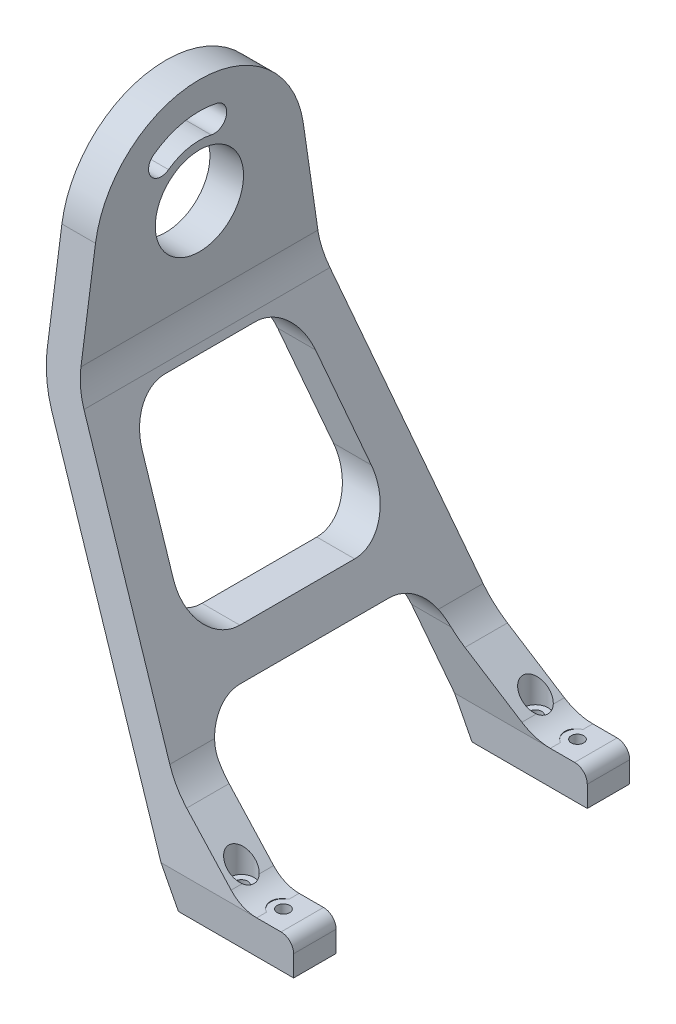
SolidWorks part; units mm, degrees
material "6061 合金"
ref_plane "前视基准面" through (0, 0, 0) normal (0, 0, 1) x (1, 0, 0)
ref_plane "上视基准面" through (0, 0, 0) normal (0, 1, 0) x (1, 0, 0)
ref_plane "右视基准面" through (0, 0, 0) normal (1, 0, 0) x (0, 0, -1)
sketch "草图1" plane through (0, 0, 0) normal (0, 0, 1) x (1, 0, 0)
  line L0 (0, 50) -> (0, 4.8715)
  line L1 (2.2402, -4.3258) -> (41.43, -80)
  line L2 (41.43, -80) -> (66.43, -80)
  arc A0 (2.2402, -4.3258) -> (0, 4.8715) centre (20, 4.8715) cw
  point P7 (0, 0)
  dimension "D5" = 20
  dimension "D1" = 80
  dimension "D2" = 41.43
  dimension "D3" = 50
  dimension "D4" = 25
extrude "拉伸-薄壁1" add sketch "草图1" along normal blind 80 thin thin type mid plane wall 8
sketch "草图9" plane through (0, 0, 0) normal (0, 0, -1) x (-1, 0, 0)
  line L0 (-53.9969, -76) -> (-36.0752, -60.9619)
  line L1 (-43.8631, -76) -> (-66.43, -76) construction
  line L2 (-5.7922, -2.4864) -> (-43.8631, -76) construction
  line L3 (-36.0752, -60.9619) -> (-43.8631, -76)
  line L4 (-43.8631, -76) -> (-53.9969, -76)
  dimension "D1" = 40
  dimension "D2" = 15
extrude "凸台-拉伸1" add sketch "草图9" against normal through all
sketch "草图2" plane through (-4, 0, 0) normal (-1, 0, 0) x (0, 0, 1)
  line L0 (80, 50) -> (0, 50) construction
  line L1 (15.2619, 28.6092) -> (0, -76)
  line L2 (0, -6.1653) -> (0, -84) construction
  line L3 (40, 85.5078) -> (40, -146.0129) construction
  line L4 (80, -84) -> (0, -84) construction
  line L5 (64.7381, 28.6092) -> (80, -76)
  line L9 (0, 50) -> (0, -76)
  line L10 (80, -76) -> (80, 50)
  line L11 (80, 50) -> (0, 50)
  arc A0 (15.2619, 28.6092) -> (64.7381, 28.6092) centre (40, 25) cw
  point P6 (40, 50)
  line M3 (0, 50) -> (0, 4.8715)
  line M5 (80, 4.8715) -> (80, 50)
  line M6 (80, 50) -> (0, 50)
  dimension "D1" = 25
  dimension "D2" = 8
extrude "切除-拉伸1" cut sketch "草图2" against normal through all contours L1 A0 L11 M3 | L1 | L5 | A0 L5 M6 M5 region at (-4, 10.8244, 72.6384) region at (-4, 10.8244, 7.3616)
fillet "圆角3" radius 10 1 edges at (53.9969, -76, 40)
sketch "草图3" plane through (0, -84, 0) normal (0, -1, 0) x (1, 0, 0)
  line L0 (-21.9643, 40) -> (81.8416, 40) construction
  line L1 (66.43, 80) -> (66.43, 0) construction
  line L2 (38.9969, 80) -> (38.9969, 0) construction
  line L3 (38.9969, 80) -> (66.43, 80) construction
  circle A0 centre (48.9969, 75) radius 1.5
  circle A1 centre (58.9969, 75) radius 1.5
  circle A2 centre (58.9969, 5) radius 1.5
  circle A3 centre (48.9969, 5) radius 1.5
  point P9 (66.43, 40)
  dimension "D4" = 3
  dimension "D1" = 10
  dimension "D2" = 10
  dimension "D3" = 5
extrude "切除-拉伸2" cut sketch "草图3" against normal through all
sketch "草图5" plane through (-4, 0, 0) normal (-1, 0, 0) x (0, 0, 1)
  line L0 (10.1059, -76) -> (10.1059, -84)
  line L1 (0, -76) -> (10.1885, -6.1653) construction
  line L2 (10.1059, -76) -> (13.6073, -52)
  line L3 (20.6103, -4) -> (59.3897, -4)
  line L4 (59.3897, -4) -> (65.2255, -44)
  line L5 (14.7745, -44) -> (65.2255, -44)
  line L6 (80, -84) -> (0, -84) construction
  line L7 (40, 64.2186) -> (40, -117.6272) construction
  line L8 (10.1059, -84) -> (69.8941, -84)
  line L9 (69.8941, -84) -> (69.8941, -76)
  line L10 (13.6073, -52) -> (66.3927, -52)
  line L11 (66.3927, -52) -> (69.8941, -76)
  line L12 (14.7745, -44) -> (20.6103, -4)
  dimension "D1" = 10
  dimension "D2" = 8
  dimension "D3" = 80
  dimension "D4" = 8
  dimension "D5" = 40
sketch "草图6" plane through (4, 0, 0) normal (1, 0, 0) x (0, 0, -1)
  line L0 (-49.1107, 37.5398) -> (-40, 25) construction
  line L1 (-40, 25) -> (-36.5133, 40.1027) construction
  line L2 (-40, 67.7902) -> (-40, -22.8803) construction
  circle A0 centre (-40, 25) radius 10.5
  arc A1 (-49.1107, 37.5398) -> (-36.5133, 40.1027) centre (-40, 25) cw construction
  arc A2 (-35.8384, 43.0258) -> (-50.874, 39.9668) centre (-40, 25) ccw
  arc A3 (-37.1881, 37.1796) -> (-47.3473, 35.1127) centre (-40, 25) ccw
  arc A4 (-37.1881, 37.1796) -> (-35.8384, 43.0258) centre (-36.5133, 40.1027) ccw
  arc A5 (-50.874, 39.9668) -> (-47.3473, 35.1127) centre (-49.1107, 37.5398) ccw
  point P5 (-43.0902, 40.1888)
  point P11 (-40, 25)
  dimension "D1" = 21
  dimension "D3" = 3
  dimension "D2" = 15.5
  dimension "D4" = 36
  dimension "D5" = 13
extrude "切除-拉伸5" cut sketch "草图6" against normal through all
ref_plane "基准面1" through (0, 0, 40) normal (0, 0, 1) x (1, 0, 0)
sketch "草图8" plane through (0, 0, 40) normal (0, 0, 1) x (1, 0, 0)
  line L0 (88.9969, 55.6878) -> (88.9969, -81.9949) construction
  dimension "D1" = 50
extrude "切除-拉伸6" cut sketch "草图5" against normal through all
fillet "圆角2" radius 10 6 edges at (2.138, -4, 59.3897) (26.9295, -52, 66.3927) (26.9295, -52, 13.6073) (22.7865, -44, 65.2255) (22.7865, -44, 14.7745) (2.138, -4, 20.6103)
ref_plane "基准面2" through (0, -66, 0) normal (0, 1, 0) x (1, 0, 0)
sketch "草图10" plane through (0, -66, 0) normal (0, 1, 0) x (1, 0, 0)
  circle A0 centre (48.9969, -5) radius 3
  circle A1 centre (58.9969, -5) radius 3
  circle A2 centre (58.9969, -75) radius 3
  circle A3 centre (48.9969, -75) radius 3
  dimension "D1" = 6
  dimension "D2" = 6
  dimension "D3" = 6
  dimension "D4" = 6
extrude "切除-拉伸7" cut sketch "草图10" against normal blind 10
fillet "圆角4" radius 3 2 edges at (66.43, -76, 5.0529) (66.43, -76, 74.9471)
fillet "圆角5" radius 20 2 edges at (36.0752, -60.9619, 7.2469) (36.0752, -60.9619, 72.7531)
